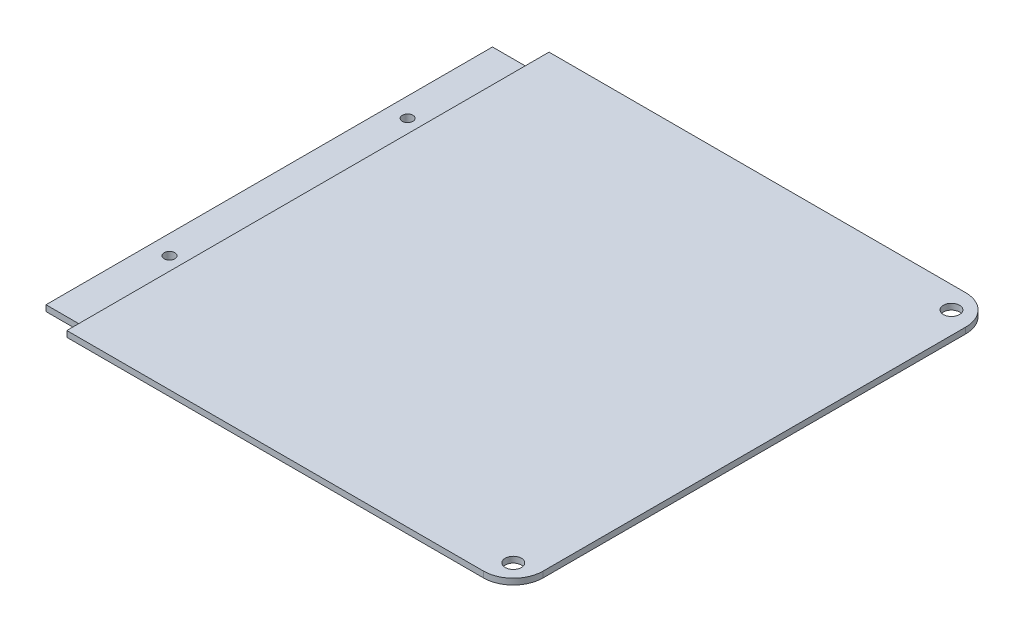
SolidWorks part; units mm, degrees
material "6061-T6 (SS)"
ref_plane "Front Plane" through (0, 0, 0) normal (0, 0, 1) x (1, 0, 0)
ref_plane "Top Plane" through (0, 0, 0) normal (0, 1, 0) x (1, 0, 0)
ref_plane "Right Plane" through (0, 0, 0) normal (1, 0, 0) x (0, 0, -1)
sketch "Sketch1" plane through (0, 0, 0) normal (0, 1, 0) x (1, 0, 0)
  line L1 (-49.8475, -51.435) -> (49.8475, -51.435)
  line L2 (-49.8475, -51.435) -> (-49.8475, 51.435)
  line L3 (-49.8475, 51.435) -> (49.8475, 51.435)
  line L4 (49.8475, -51.435) -> (49.8475, 51.435)
  line L5 (-49.8475, -51.435) -> (49.8475, 51.435) construction
  line L6 (-49.8475, 51.435) -> (49.8475, -51.435) construction
  point P0 (0, 0)
  dimension "D1" = 102.87
  dimension "D2" = 99.695
extrude "Boss-Extrude1" add sketch "Sketch1" along normal blind 2.54
hole_wizard "#4 Clearance Hole1" positions "Sketch2" profile "Sketch3" hole size "#4" standard "ANSI Inch"
sketch "Sketch2" plane through (0, 2.54, 0) normal (0, 1, 0) x (1, 0, 0)
  line L0 (49.8475, 51.435) -> (-49.8475, 51.435) construction
  line L1 (-49.8475, -51.435) -> (49.8475, -51.435) construction
  line L2 (49.8475, -51.435) -> (49.8475, 51.435) construction
  point P0 (45.1485, 46.736)
  point P2 (45.1485, -46.736)
  dimension "D1" = 4.699
  dimension "D2" = 4.699
  dimension "D3" = 4.699
sketch "Sketch3" plane through (45.1485, 2.54, -46.736) normal (1, 0, 0) x (0, 0, 1)
  line L0 (0, 0) -> (0, 5.9908)
  line L1 (0, 5.9908) -> (1.7272, 4.953)
  line L2 (1.7272, 4.953) -> (1.7272, 0)
  line L5 (1.7272, 0) -> (0, 0)
  line L10 (0, 5.9908) -> (-1.7272, 4.953) construction
  line L11 (0, -6.35) -> (0, 107.95) construction
  dimension "Hole Dia." = 3.4544
  dimension "Hole Depth" = 4.953
  dimension "Drill Angle" = 118
fillet "Fillet1" radius 6.35 2 edges at (49.8475, 1.27, 51.435) (49.8475, 1.27, -51.435)
sketch "Sketch4" plane through (-49.8475, 0, 0) normal (-1, 0, 0) x (0, 0, 1)
  line L0 (51.435, 2.54) -> (51.435, 0) construction
  line L1 (-51.435, 0) -> (51.435, 0)
  line L2 (-51.435, 0) -> (-51.435, 1.27)
  line L3 (-51.435, 1.27) -> (51.435, 1.27)
  line L4 (51.435, 0) -> (51.435, 1.27)
extrude "Boss-Extrude2" add sketch "Sketch4" along normal blind 3.81
sketch "Sketch5" plane through (-49.8475, 0, 0) normal (-1, 0, 0) x (0, 0, 1)
  line L1 (-51.435, 2.54) -> (51.435, 2.54)
  line L2 (-51.435, 2.54) -> (-51.435, 1.27)
  line L3 (-51.435, 1.27) -> (51.435, 1.27)
  line L4 (51.435, 2.54) -> (51.435, 1.27)
extrude "Cut-Extrude1" cut sketch "Sketch5" against normal blind 4.445
hole_wizard "#4-40 Tapped Hole1" positions "Sketch6" profile "Sketch7" tap size "#4-40" standard "ANSI Inch"
sketch "Sketch6" plane through (0, 1.27, 0) normal (0, 1, 0) x (1, 0, 0)
  line L0 (-49.53, 25.4) -> (-49.53, -25.4) construction
  line L1 (-49.53, 0) -> (0, 0) construction
  line L2 (-53.6575, 0) -> (-45.4025, 0) construction
  line L3 (-53.6575, -51.435) -> (-53.6575, 51.435) construction
  line L4 (-45.4025, 51.435) -> (-45.4025, -51.435) construction
  point P0 (-49.53, 25.4)
  point P2 (-49.53, -25.4)
  dimension "D1" = 50.8
sketch "Sketch7" plane through (-49.53, 1.27, -25.4) normal (1, 0, 0) x (0, 0, 1)
  line L0 (0, 0) -> (0, 8.2738)
  line L1 (0, 8.2738) -> (1.1303, 7.5946)
  line L2 (1.1303, 7.5946) -> (1.1303, 0)
  line L5 (1.1303, 0) -> (0, 0)
  line L10 (0, 8.2738) -> (-1.1303, 7.5946) construction
  line L11 (0, -6.35) -> (0, 107.95) construction
  dimension "Tap Drill Dia." = 2.2606
  dimension "Tap Drill Depth" = 7.5946
  dimension "Drill Angle" = 118
cosmetic thread "Hole Thread1" parameters "D1"=1.27, "D2"=2.8448
cosmetic thread "Hole Thread2" parameters "D1"=1.27, "D2"=2.8448
ref_plane "Plane2" through (0, 1.74, 0) normal (0, 1, 0) x (1, 0, 0)
sketch "Sketch8" plane through (0, 0, 0) normal (0, -1, 0) x (1, 0, 0)
  line L4 (-53.6575, 47.625) -> (41.8465, 47.625)
  line L5 (41.8465, 47.625) -> (41.8465, 44.704)
  line L6 (43.1165, 43.434) -> (46.0375, 43.434)
  line L7 (46.0375, 43.434) -> (46.0375, -43.434)
  line L8 (49.8475, -45.085) -> (49.8475, 45.085)
  line L9 (43.4975, 51.435) -> (-53.6575, 51.435)
  line L10 (-53.6575, 51.435) -> (-53.6575, -51.435)
  line L11 (-53.6575, -51.435) -> (43.4975, -51.435)
  line L12 (49.8475, -45.085) -> (49.8475, 45.085)
  line L13 (43.4975, 51.435) -> (-53.6575, 51.435)
  line L14 (-53.6575, 51.435) -> (-53.6575, -51.435)
  line L15 (-53.6575, -51.435) -> (43.4975, -51.435)
  line L16 (46.0375, -43.434) -> (43.1165, -43.434)
  line L17 (41.8465, -44.704) -> (41.8465, -47.625)
  line L18 (41.8465, -47.625) -> (-53.6575, -47.625)
  arc A2 (41.8465, 44.704) -> (43.1165, 43.434) centre (43.1165, 44.704) ccw
  arc A3 (43.1165, -43.434) -> (41.8465, -44.704) centre (43.1165, -44.704) ccw
  arc A4 (49.8475, 45.085) -> (43.4975, 51.435) centre (43.4975, 45.085) ccw
  arc A5 (43.4975, -51.435) -> (49.8475, -45.085) centre (43.4975, -45.085) ccw
  arc A6 (49.8475, 45.085) -> (43.4975, 51.435) centre (43.4975, 45.085) ccw
  arc A7 (43.4975, -51.435) -> (49.8475, -45.085) centre (43.4975, -45.085) ccw
  circle M21 centre (45.1485, -46.736) radius 1.7272
  circle M22 centre (45.1485, 46.736) radius 1.7272
  line M23 (49.8475, -45.085) -> (49.8475, 45.085)
  arc M24 (49.8475, 45.085) -> (43.4975, 51.435) centre (43.4975, 45.085) ccw
  line M25 (43.4975, 51.435) -> (-53.6575, 51.435)
  line M26 (-53.6575, 51.435) -> (-53.6575, -51.435)
  line M27 (-53.6575, -51.435) -> (43.4975, -51.435)
  arc M28 (43.4975, -51.435) -> (49.8475, -45.085) centre (43.4975, -45.085) ccw
  dimension "D7" = 1.27
  dimension "D2" = 8.001
  dimension "D3" = 8.001
  dimension "D4" = 8.001
  dimension "D5" = 3.81
  dimension "D6" = 3.81
  dimension "D1" = 0
extrude "Cut-Extrude2" cut sketch "Sketch8" against normal blind 1.27 contours L17 L18 L14 L4 L5 L6 L7 L16 M27 M28 M23 M24 M25 M26 M21 M22 region at (-52.1982, 0, 49.53)
sketch "Sketch9" plane through (0, 0, 0) normal (0, -1, 0) x (1, 0, 0)
  line L0 (-44.1325, 41.275) -> (-44.1325, -41.275)
  line L1 (-44.1325, 0.9525) -> (39.6875, 0.9525)
  line L2 (-44.1325, -0.9525) -> (39.6875, -0.9525)
  line L3 (-2.2225, 0.9525) -> (-2.2225, -0.9525) construction
  line L4 (0, 0) -> (-2.2225, 0) construction
  line L5 (-2.2225, 0) -> (-2.2225, 41.275) construction
  line L6 (-2.2225, 20.6375) -> (39.6875, 20.6375) construction
  line L7 (10.4775, 21.2725) -> (11.7475, 21.2725) construction
  line L8 (39.6875, 20.0025) -> (-44.1325, 20.0025)
  line L9 (-11.6026, 21.2725) -> (-11.6026, 20.0025) construction
  line L10 (-45.4025, 47.625) -> (-45.4025, 51.435) construction
  line L16 (36.3116, 41.275) -> (-47.3075, 41.275)
  line L17 (-47.3075, 41.275) -> (-47.3075, -41.275)
  line L18 (-47.3075, -41.275) -> (36.3116, -41.275)
  line L21 (39.6875, -37.8991) -> (39.6875, 37.8991)
  line L24 (11.7475, 21.2725) -> (13.0175, 21.2725) construction
  line L26 (-44.1325, -41.275) -> (36.3116, -41.275)
  line L29 (39.6875, -37.8991) -> (39.6875, 37.8991)
  line L33 (-11.6026, 20.6375) -> (-2.2225, 20.6375) construction
  line L34 (39.6875, 21.2725) -> (26.9875, 41.275)
  line L35 (25.7175, 41.275) -> (38.4175, 21.2725)
  line L36 (25.7175, 41.275) -> (13.0175, 21.2725)
  line L37 (24.4475, 41.275) -> (11.7475, 21.2725)
  line L38 (11.7475, 21.2725) -> (-0.9525, 41.275)
  line L39 (-2.2225, 41.275) -> (10.4775, 21.2725)
  line L40 (24.4475, 41.275) -> (25.7175, 41.275) construction
  line L41 (25.7175, 41.275) -> (26.9875, 41.275) construction
  line L42 (-2.2225, 41.275) -> (-0.9525, 41.275) construction
  line L43 (11.7475, 21.2725) -> (11.7475, 31.2737) construction
  line L44 (5.3975, 31.2737) -> (18.0975, 31.2737) construction
  line L45 (25.7175, 41.275) -> (25.7175, 31.2737) construction
  line L46 (19.3675, 31.2737) -> (32.0675, 31.2737) construction
  line L47 (-44.1325, 41.275) -> (36.3116, 41.275)
  line L48 (-44.1325, 21.2725) -> (39.6875, 21.2725)
  line L49 (-44.1325, 21.2725) -> (-31.4325, 41.275)
  line L50 (-30.1625, 41.275) -> (-42.8625, 21.2725)
  line L51 (-30.1625, 41.275) -> (-17.4625, 21.2725)
  line L52 (-28.8925, 41.275) -> (-16.1925, 21.2725)
  line L53 (-16.1925, 21.2725) -> (-3.4925, 41.275)
  line L54 (-2.2225, 41.275) -> (-14.9225, 21.2725)
  line L55 (39.6875, 20.0025) -> (26.9875, 0)
  line L56 (25.7175, 0) -> (38.4175, 20.0025)
  line L57 (25.7175, 0) -> (13.0175, 20.0025)
  line L58 (24.4475, 0) -> (11.7475, 20.0025)
  line L59 (11.7475, 20.0025) -> (-0.9525, 0)
  line L60 (-2.2225, 0) -> (10.4775, 20.0025)
  line L61 (-2.2225, 0) -> (-14.9225, 20.0025)
  line L62 (-16.1925, 20.0025) -> (-3.4925, 0)
  line L63 (-28.8925, 0) -> (-16.1925, 20.0025)
  line L64 (-30.1625, 0) -> (-17.4625, 20.0025)
  line L65 (-30.1625, 0) -> (-42.8625, 20.0025)
  line L66 (-44.1325, 20.0025) -> (-31.4325, 0)
  arc A4 (39.6875, -37.8991) -> (36.3116, -41.275) centre (43.1165, -44.704) ccw
  arc A5 (36.3116, 41.275) -> (39.6875, 37.8991) centre (43.1165, 44.704) ccw
  arc A6 (39.6875, -37.8991) -> (36.3116, -41.275) centre (43.1165, -44.704) ccw
  arc A7 (36.3116, 41.275) -> (39.6875, 37.8991) centre (43.1165, 44.704) ccw
  dimension "D2" = 1.27
  dimension "D4" = 1.905
  dimension "D5" = 1.27
  dimension "D6" = 1.27
  dimension "D1" = 6.35
ref_plane "Plane1" through (0, 0.47, 0) normal (0, 1, 0) x (1, 0, 0)
extrude "Cut-Extrude3" cut sketch "Sketch9" against normal up to surface (1.74 mm away) contours L66 L1 | L65 L1 L64 L8 | L63 L1 L62 | L61 L1 L60 L8 | L58 L59 L1 | L57 L1 L56 L8 | L29 L55 L1 | A7 L47 L34 L29 | L36 L48 L35 | L47 L38 L37 | L39 L54 L48 | L52 L53 L47 | L51 L50 L48 | L49 L47 region at (-39.8992, 0, 34.6075) region at (-40.1008, 0, 7.3025) region at (-30.1625, 0, 27.94) region at (-30.1625, 0, 13.3639) region at (-16.1925, 0, 34.6075) region at (-16.1925, 0, 7.3025) region at (-2.2225, 0, 27.94) region at (35.6558, 0, 7.3025) region at (-2.2225, 0, 13.3639) region at (11.7475, 0, 34.6075) region at (25.7175, 0, 13.3639) region at (35.2818, 0, 34.2948) region at (11.7475, 0, 7.3025) region at (25.7175, 0, 27.94) up to plane "Plane2"
mirror "Mirror1" about plane through (0, 0, 0) normal (0, 0, 1) of "Cut-Extrude3"
sketch "Sketch13" plane through (0, 0, 0) normal (0, -1, 0) x (1, 0, 0)
  line L0 (-53.6575, -47.625) -> (-53.6575, 47.625) construction
  line L1 (-44.1325, 30.1625) -> (-53.6575, 30.1625)
  line L2 (-44.1325, 30.1625) -> (-44.1325, 20.6375)
  line L3 (-44.1325, 20.6375) -> (-53.6575, 20.6375)
  line L4 (-53.6575, 30.1625) -> (-53.6575, 20.6375)
  line L5 (-44.1325, 41.275) -> (-44.1325, 21.2725) construction
  line L7 (-44.1325, -30.1625) -> (-53.6575, -30.1625)
  line L8 (-44.1325, -30.1625) -> (-44.1325, -20.6375)
  line L9 (-44.1325, -20.6375) -> (-53.6575, -20.6375)
  line L10 (-53.6575, -30.1625) -> (-53.6575, -20.6375)
  line L11 (-49.53, 25.4) -> (-44.1325, 25.4) construction
  line L12 (-49.53, -25.4) -> (-44.1325, -25.4) construction
extrude "Boss-Extrude3" add sketch "Sketch13" along normal blind 2.54
hole_wizard "#4-40 Tapped Hole2" positions "Sketch14" profile "Sketch15" tap size "#4-40" standard "ANSI Inch"
sketch "Sketch14" plane through (0, 1.27, 0) normal (0, 1, 0) x (1, 0, 0)
  point P0 (-49.53, -25.4)
  point P3 (-49.53, 25.4)
sketch "Sketch15" plane through (-49.53, 1.27, 25.4) normal (1, 0, 0) x (0, 0, 1)
  line L0 (0, 0) -> (0, 8.2738)
  line L1 (0, 8.2738) -> (1.1303, 7.5946)
  line L2 (1.1303, 7.5946) -> (1.1303, 0)
  line L5 (1.1303, 0) -> (0, 0)
  line L10 (0, 8.2738) -> (-1.1303, 7.5946) construction
  line L11 (0, -6.35) -> (0, 107.95) construction
  dimension "Tap Drill Dia." = 2.2606
  dimension "Tap Drill Depth" = 7.5946
  dimension "Drill Angle" = 118
cosmetic thread "Hole Thread3" parameters "D1"=3.81, "D2"=2.8448
chamfer "Chamfer1" distance 2.54 angle 30 8 edges at (-44.1325, -2.54, -25.4) (-48.895, -2.54, -30.1625) (-48.895, -2.54, -20.6375) (-53.6575, -2.54, -25.4) (-48.895, -2.54, 20.6375) (-44.1325, -2.54, 25.4) (-48.895, -2.54, 30.1625) (-53.6575, -2.54, 25.4) first distance on face at (-44.1325, -0.2, -28.3369) first distance on face at (-48.895, -1.27, -30.1625) first distance on face at (-48.895, -1.27, -20.6375) first distance on face at (-53.6575, -0.635, 0) first distance on face at (-48.895, -1.27, 20.6375) first distance on face at (-44.1325, -0.2, 28.3369) first distance on face at (-48.895, -1.27, 30.1625)
sketch "Sketch16" plane through (0, 2.54, 0) normal (0, 1, 0) x (1, 0, 0)
  circle A0 centre (47.9876, 49.5751) radius 5
  arc A1 (49.8475, 45.085) -> (43.4975, 51.435) centre (43.4975, 45.085) ccw construction
  circle A2 centre (47.9876, -49.5751) radius 5
  arc A3 (43.4975, -51.435) -> (49.8475, -45.085) centre (43.4975, -45.085) ccw construction
  circle A4 centre (-45.4025, 51.435) radius 5
  circle A5 centre (-45.4025, -51.435) radius 5
  dimension "D1" = 10
extrude "Printing Pads" [suppressed] add sketch "Sketch16" against normal blind 0.4
